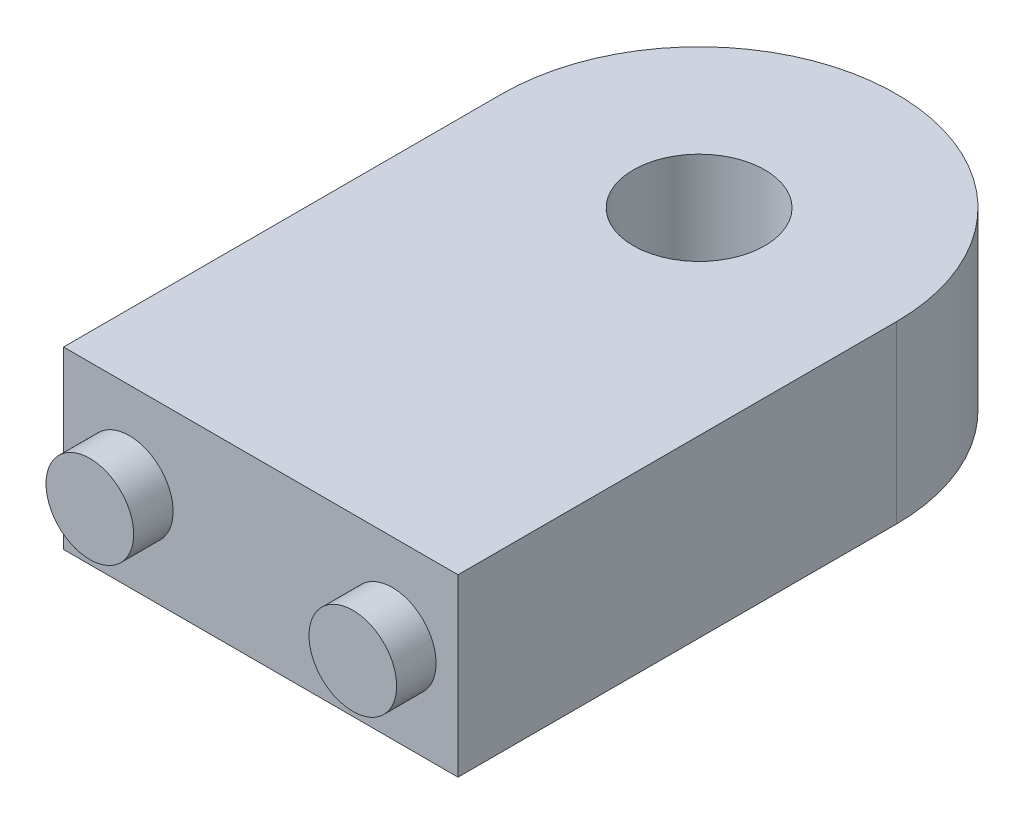
SolidWorks part; units mm, degrees
ref_plane "Front Plane" through (0, 0, 0) normal (0, 0, 1) x (1, 0, 0)
ref_plane "Top Plane" through (0, 0, 0) normal (0, 1, 0) x (1, 0, 0)
ref_plane "Right Plane" through (0, 0, 0) normal (1, 0, 0) x (0, 0, -1)
sketch "Sketch1" plane through (0, 0, 0) normal (0, 1, 0) x (1, 0, 0)
  line L1 (-225, -250) -> (225, -250)
  line L2 (-225, -250) -> (-225, 250)
  line L3 (-225, 250) -> (225, 250)
  line L4 (225, -250) -> (225, 250)
  line L5 (-225, -250) -> (225, 250) construction
  line L6 (-225, 250) -> (225, -250) construction
  arc A0 (-225, 250) -> (225, 250) centre (0, 250) cw
  point P0 (0, 0)
  dimension "D1" = 500
  dimension "D2" = 450
extrude "Boss-Extrude1" add sketch "Sketch1" along normal blind 200 contours A0 L3 | L1 L4 L3 L2 region at (0, 0, 0) region at (0, 0, -345.493)
sketch "Sketch2" plane through (0, 200, 0) normal (0, 1, 0) x (1, 0, 0)
  line L0 (225, 250) -> (-225, 250)
  circle A0 centre (0, 250) radius 75
  dimension "D1" = 150
extrude "Cut-Extrude1" cut sketch "Sketch2" against normal through all contours A0
sketch "Sketch4" plane through (0, 0, 250) normal (0, 0, 1) x (1, 0, 0)
  line L0 (0, 0) -> (0, 200)
  line L1 (-225, 200) -> (225, 200) construction
  line L2 (0, 100) -> (150, 100)
  circle A0 centre (150, 100) radius 50
extrude "Boss-Extrude2" add sketch "Sketch4" along normal blind 45 contours A0 region at (150, 51.4142, 250)
sketch "Sketch5" plane through (0, 0, 250) normal (0, 0, 1) x (1, 0, 0)
  line L0 (0, 0) -> (0, 200)
  line L1 (-225, 200) -> (225, 200) construction
  line L2 (0, 100) -> (-150, 100)
  circle A0 centre (-150, 100) radius 50
  dimension "D1" = 150
extrude "Boss-Extrude3" add sketch "Sketch5" along normal blind 45 contours A0 region at (-198.5858, 100, 250)
